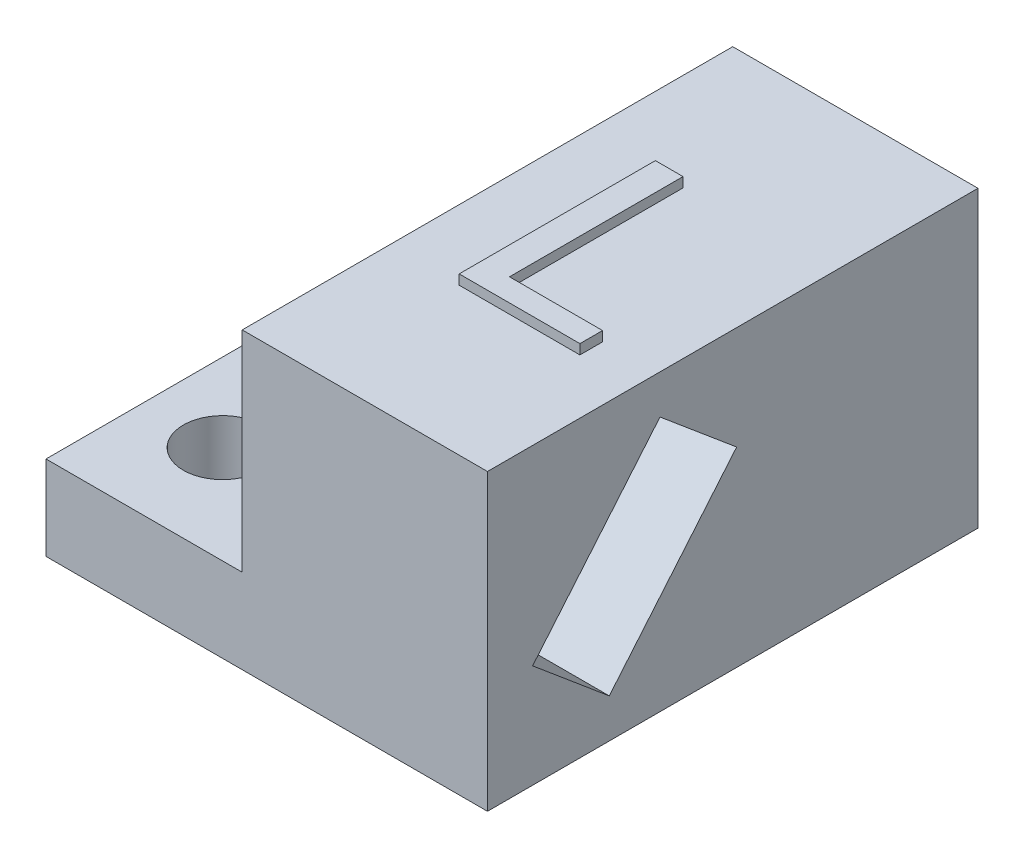
SolidWorks part; units mm, degrees
ref_plane "Спереди" through (0, 0, 0) normal (0, 0, 1) x (1, 0, 0)
ref_plane "Сверху" through (0, 0, 0) normal (0, 1, 0) x (1, 0, 0)
ref_plane "Справа" through (0, 0, 0) normal (1, 0, 0) x (0, 0, -1)
sketch "Sketch1" plane through (0, 0, 0) normal (0, 1, 0) x (1, 0, 0)
  line L1 (12.5, -25) -> (-12.5, -25)
  line L2 (12.5, -25) -> (12.5, 25)
  line L3 (12.5, 25) -> (-12.5, 25)
  line L4 (-12.5, -25) -> (-12.5, 25)
  line L5 (12.5, -25) -> (-12.5, 25) construction
  line L6 (12.5, 25) -> (-12.5, -25) construction
  point P0 (0, 0)
  dimension "D1" = 25
  dimension "D2" = 50
extrude "Boss-Extrude1" add sketch "Sketch1" along normal blind 30
sketch "Sketch2" plane through (-12.5, 0, 0) normal (-1, 0, 0) x (0, 0, 1)
  line L0 (-25, 4.3025) -> (25, 4.3025) construction
  line L1 (-25, 30) -> (-25, 0) construction
  line L2 (25, 30) -> (25, 0) construction
  line L4 (25, 8.605) -> (-25, 8.605)
  line L5 (25, 8.605) -> (25, 0)
  line L6 (25, 0) -> (-25, 0)
  line L7 (-25, 8.605) -> (-25, 0)
  line L8 (25, 8.605) -> (-25, 0) construction
  line L9 (25, 0) -> (-25, 8.605) construction
  point P6 (0, 4.3025)
extrude "Boss-Extrude2" add sketch "Sketch2" along normal blind 20
sketch "Sketch3" plane through (0, 8.605, 0) normal (0, 1, 0) x (1, 0, 0)
  line L0 (-24.5, -25) -> (-24.5, 25) construction
  line L1 (-32.5, 25) -> (-12.5, 25) construction
  line L2 (-32.5, -25) -> (-12.5, -25) construction
  circle A0 centre (-24.5, 15) radius 4
  circle A1 centre (-24.5, -15) radius 4
  dimension "D1" = 8
  dimension "D2" = 8
  dimension "D3" = 10
  dimension "D4" = 10
extrude "Cut-Extrude1" cut sketch "Sketch3" against normal through all
sketch "Sketch4" plane through (12.5, 0, 0) normal (1, 0, 0) x (0, 0, -1)
  line L0 (-10, 30) -> (-10, 0) construction
  line L1 (-12.5853, 3.9847) -> (0.399, 19.4588)
  line L2 (-12.5853, 3.9847) -> (-20.399, 10.5412)
  line L3 (-25, 30) -> (25, 30) construction
  line L4 (-4.9, 4.9) -> (-15.1, 4.9) construction
  line L5 (-4.9, 4.9) -> (-4.9, 25.1) construction
  line L6 (-4.9, 25.1) -> (-15.1, 25.1) construction
  line L7 (-15.1, 4.9) -> (-15.1, 25.1) construction
  line L8 (-4.9, 4.9) -> (-15.1, 25.1) construction
  line L9 (-4.9, 25.1) -> (-15.1, 4.9) construction
  line L10 (-25, 0) -> (25, 0) construction
  line L11 (0.399, 19.4588) -> (-7.4147, 26.0153)
  line L12 (-20.399, 10.5412) -> (-7.4147, 26.0153)
  line L13 (-3.5078, 22.737) -> (-16.4922, 7.263) construction
  line L14 (-6.0932, 11.7218) -> (-13.9068, 18.2782) construction
  line L15 (-25, 30) -> (-25, 0) construction
  point P6 (-10, 15)
  point P12 (-10, 15)
  point P13 (-10, 15)
  point P15 (0, 0)
  point P19 (0, 0)
  dimension "D1" = 20.2
  dimension "D2" = 10.2
  dimension "D3" = 15
  dimension "D4" = 10.2
  dimension "D5" = 20.2
  dimension "D6" = 40
extrude "Cut-Extrude2" cut sketch "Sketch4" against normal blind 20
sketch "Sketch5" plane through (0, 30, 0) normal (0, 1, 0) x (1, 0, 0)
  line L0 (12.5, -10) -> (-12.5, -10) construction
  line L1 (12.5, -25) -> (12.5, 25) construction
  line L2 (-12.5, 25) -> (-12.5, -25) construction
  text T0 "L" font "Arial" height 20
  dimension "D1" = 15
extrude "Boss-Extrude3" add sketch "Sketch5" along normal blind 1
